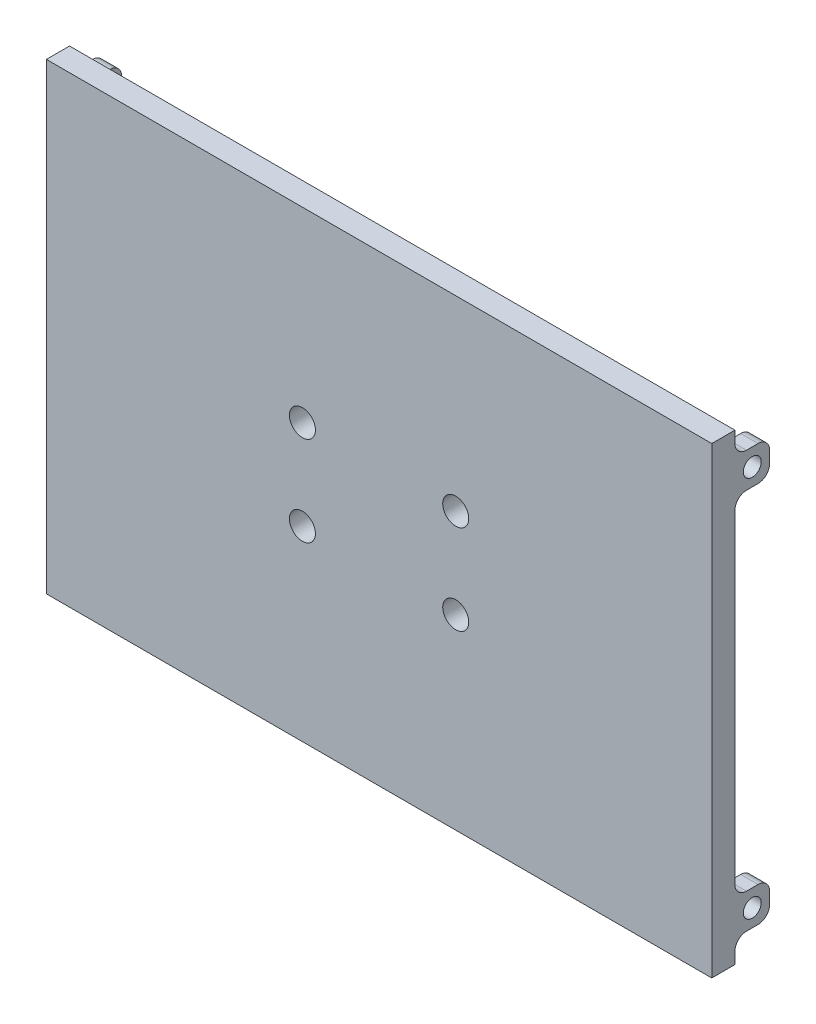
SolidWorks part; units mm, degrees
ref_plane "Front Plane" through (0, 0, 0) normal (1, 0, 0) x (0, 1, 0)
ref_plane "Top Plane" through (0, 0, 0) normal (0, 0, 1) x (0, 1, 0)
ref_plane "Right Plane" through (0, 0, 0) normal (0, 1, 0) x (-1, 0, 0)
sketch "Sketch1" plane through (0, 0, 0) normal (0, 0, 1) x (0, 1, 0)
  line L1 (-40, -57.5) -> (40, -57.5)
  line L2 (-40, -57.5) -> (-40, 57.5)
  line L3 (-40, 57.5) -> (40, 57.5)
  line L4 (40, -57.5) -> (40, 57.5)
  line L5 (-40, -57.5) -> (40, 57.5) construction
  line L6 (-40, 57.5) -> (40, -57.5) construction
  point P0 (0, 0)
  dimension "D1" = 115
  dimension "D2" = 80
extrude "Boss-Extrude1" add sketch "Sketch1" along normal blind 4
sketch "Sketch2" plane through (0, 0, 4) normal (0, 0, 1) x (1, 0, 0)
  line L0 (0, 0) -> (0, 40) construction
  line L1 (57.5, 40) -> (-57.5, 40) construction
  line L2 (0, 0) -> (57.5, 0) construction
  line L3 (57.5, -40) -> (57.5, 40) construction
  circle A0 centre (13.25, 7.75) radius 2.25
  circle A1 centre (-13.25, 7.75) radius 2.25
  circle A2 centre (13.25, -7.75) radius 2.25
  circle A3 centre (-13.25, -7.75) radius 2.25
  dimension "D1" = 4.5
  dimension "D2" = 7.75
  dimension "D3" = 13.25
extrude "Cut-Extrude1" cut sketch "Sketch2" against normal up to next
sketch "Sketch4" plane through (0, 0, 0) normal (0, 0, -1) x (1, 0, 0)
  line L0 (0, 0) -> (0, 40) construction
  line L1 (-57.5, 40) -> (57.5, 40) construction
  line L2 (0, 0) -> (57.5, 0) construction
  line L3 (57.5, 40) -> (57.5, -40) construction
  line L4 (-57.5, 36) -> (-54.5, 36)
  line L5 (57.5, 30) -> (54.5, 30)
  line L6 (57.5, 30) -> (57.5, 36)
  line L7 (57.5, 36) -> (54.5, 36)
  line L8 (54.5, 30) -> (54.5, 36)
  line L9 (-54.5, 30) -> (-54.5, 36)
  line L10 (-57.5, 30) -> (-54.5, 30)
  line L11 (-57.5, 30) -> (-57.5, 36)
  line L12 (-57.5, -30) -> (-57.5, -36)
  line L13 (-57.5, -30) -> (-54.5, -30)
  line L14 (-54.5, -30) -> (-54.5, -36)
  line L15 (-57.5, -36) -> (-54.5, -36)
  line L16 (57.5, -36) -> (54.5, -36)
  line L17 (54.5, -30) -> (54.5, -36)
  line L18 (57.5, -30) -> (54.5, -30)
  line L19 (57.5, -30) -> (57.5, -36)
  dimension "D1" = 3
  dimension "D2" = 6
  dimension "D3" = 30
extrude "Boss-Extrude3" add sketch "Sketch4" along normal blind 6
sketch "Sketch5" plane through (57.5, 0, 0) normal (1, 0, 0) x (0, 1, 0)
  line L2 (-36, -3) -> (-30, -3) construction
  line L3 (-36, -6) -> (-36, 0) construction
  line L4 (-30, -6) -> (-30, 0) construction
  line L5 (0, 4) -> (0, 0) construction
  line L6 (-40, 4) -> (40, 4) construction
  circle A0 centre (-33, -3) radius 1.55
  circle A1 centre (33, -3) radius 1.55
  dimension "D1" = 3.1
extrude "Cut-Extrude2" cut sketch "Sketch5" against normal through all both and the other way through all
fillet "Fillet1" radius 2 16 edges at (-56, 30, 0) (-56, 36, 0) (-56, 36, -6) (-56, 30, -6) (-56, -30, 0) (-56, -30, -6) (-56, -36, -6) (-56, -36, 0) (56, 30, 0) (56, 30, -6) (56, 36, -6) (56, 36, 0) (56, -30, 0) (56, -30, -6) (56, -36, -6) (56, -36, 0)
